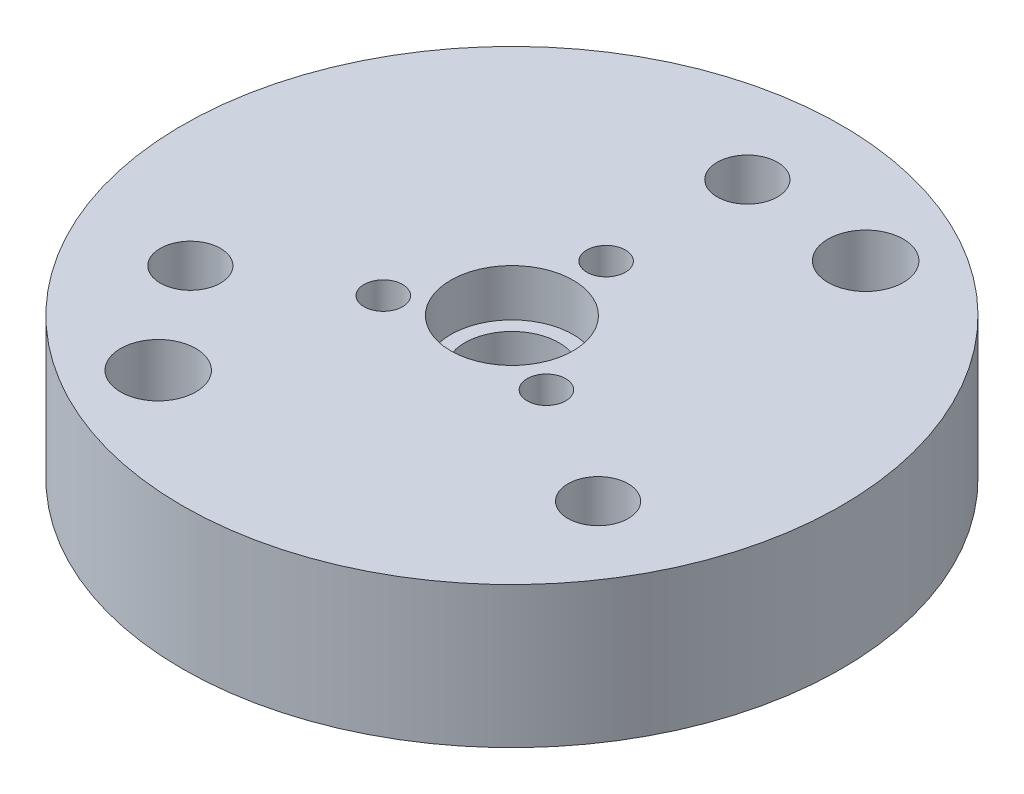
SolidWorks part; units mm, degrees
material "Plain Carbon Steel"
ref_plane "Front Plane" through (0, 0, 0) normal (0, 0, 1) x (1, 0, 0)
ref_plane "Top Plane" through (0, 0, 0) normal (0, 1, 0) x (1, 0, 0)
ref_plane "Right Plane" through (0, 0, 0) normal (1, 0, 0) x (0, 0, -1)
sketch "Sketch1" plane through (0, 0, 0) normal (0, 1, 0) x (1, 0, 0)
  circle A0 centre (0, 0) radius 35
  dimension "D1" = 70
extrude "Boss-Extrude1" add sketch "Sketch1" along normal blind 15
sketch "Sketch2" plane through (0, 15, 0) normal (0, 1, 0) x (1, 0, 0)
  circle A0 centre (0, 0) radius 5
  dimension "D1" = 10
extrude "Cut-Extrude1" cut sketch "Sketch2" against normal up to next
sketch "Sketch3" plane through (0, 15, 0) normal (0, 1, 0) x (1, 0, 0)
  circle A0 centre (0, 0) radius 6.5
  dimension "D1" = 13
extrude "Cut-Extrude2" cut sketch "Sketch3" against normal blind 5
sketch "Sketch4" plane through (0, 15, 0) normal (0, 1, 0) x (1, 0, 0)
  circle A0 centre (0, 10) radius 2.05 construction
  circle A1 centre (8.6603, -5) radius 2.05 construction
  circle A2 centre (-8.6603, -5) radius 2.05 construction
  circle A3 centre (0, 10) radius 2.05
  circle A4 centre (8.6603, -5) radius 2.05
  circle A5 centre (-8.6603, -5) radius 2.05
extrude "Cut-Extrude3" cut sketch "Sketch4" against normal up to next
hole_wizard "M6 Clearance Hole1" positions "Sketch7" profile "Sketch6" hole size "M6" standard "ISO" end condition through all
sketch "Sketch7" plane through (0, 0, 0) normal (0, -1, 0) x (-1, 0, 0)
  point P0 (0, 25)
  point P3 (21.6506, -12.5)
  point P6 (-21.6506, -12.5)
sketch "Sketch6" plane through (0, 0, -25) normal (1, 0, 0) x (0, 0, -1)
  line L0 (0, 0) -> (0, 15)
  line L1 (0, 15) -> (3.2, 15)
  line L2 (3.2, 15) -> (3.2, 0)
  line L5 (3.2, 0) -> (0, 0)
  line L11 (0, -6.35) -> (0, 107.95) construction
  dimension "Thru Hole Dia." = 6.4
  dimension "Thru Hole Depth" = 15
hole_wizard "Ø8.0mm Dowel Hole1" positions "Sketch10" profile "Sketch9" hole size "Ø8.0" standard "ISO" end condition through all
sketch "Sketch10" plane through (0, 0, 0) normal (0, -1, 0) x (-1, 0, 0)
  point P0 (-13.75, 23.8157)
  point P3 (13.75, -23.8157)
sketch "Sketch9" plane through (13.75, 0, -23.8157) normal (1, 0, 0) x (0, 0, -1)
  line L0 (0, 0) -> (0, 15)
  line L1 (0, 15) -> (4, 15)
  line L2 (4, 15) -> (4, 0)
  line L5 (4, 0) -> (0, 0)
  line L11 (0, -6.35) -> (0, 107.95) construction
  dimension "Thru Hole Dia." = 8
  dimension "Thru Hole Depth" = 15
